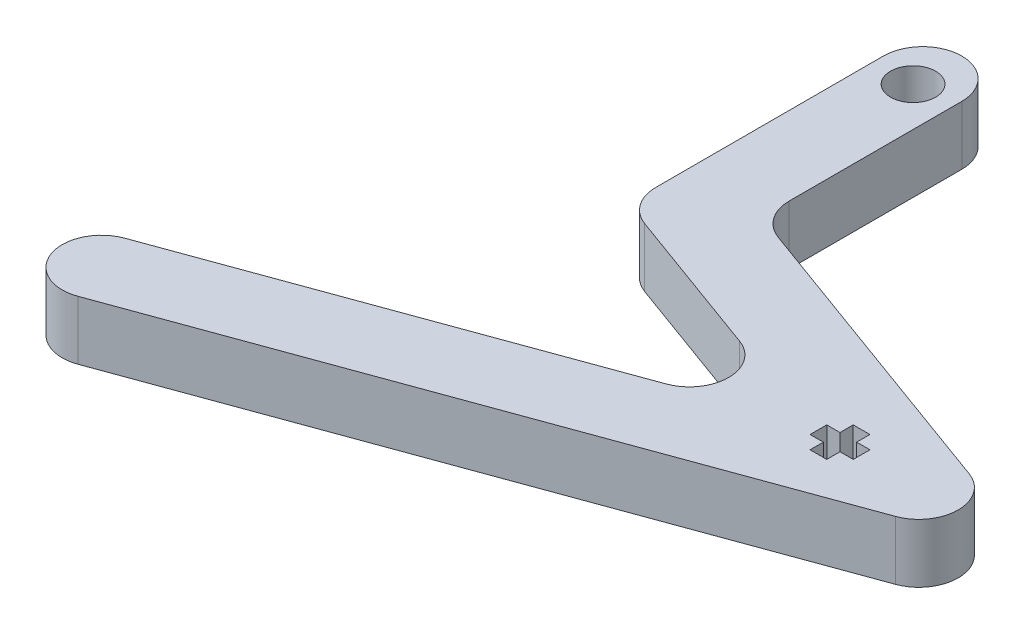
SolidWorks part; units mm, degrees
ref_plane "Front Plane" through (0, 0, 0) normal (0, 0, 1) x (1, 0, 0)
ref_plane "Top Plane" through (0, 0, 0) normal (0, 1, 0) x (1, 0, 0)
ref_plane "Right Plane" through (0, 0, 0) normal (1, 0, 0) x (0, 0, -1)
sketch "Sketch1" plane through (0, 0, 0) normal (0, 1, 0) x (1, 0, 0)
  line L16 (-80.6848, 38.8147) -> (-80.6848, 8.8147)
  line L19 (-72.6848, 14.4164) -> (-72.6848, 38.8147)
  line L22 (-72.6848, 14.4164) -> (-29.1036, -1.4459)
  line L26 (-80.6848, 8.8147) -> (-52.494, -1.4459)
  line L27 (-52.494, -1.4459) -> (-107.0151, -21.29)
  line L28 (-107.0151, -21.29) -> (-104.279, -28.8075)
  line L29 (-104.279, -28.8075) -> (-29.1036, -1.4459)
  line L30 (-80.6848, 38.8147) -> (-72.6848, 38.8147)
  line L43 (-51.0109, -0.6289) -> (-51.0109, -2.3289)
  line L44 (-51.0109, -2.3289) -> (-49.6609, -2.3289)
  line L45 (-49.6609, -2.3289) -> (-49.6609, -3.6789)
  line L46 (-49.6609, -3.6789) -> (-47.9609, -3.6789)
  line L47 (-47.9609, -3.6789) -> (-47.9609, -2.3289)
  line L48 (-47.9609, -2.3289) -> (-46.6109, -2.3289)
  line L49 (-46.6109, -2.3289) -> (-46.6109, -0.6289)
  line L50 (-46.6109, -0.6289) -> (-47.9609, -0.6289)
  line L51 (-47.9609, -0.6289) -> (-47.9609, 0.7211)
  line L52 (-47.9609, 0.7211) -> (-49.6609, 0.7211)
  line L53 (-49.6609, 0.7211) -> (-49.6609, -0.6289)
  line L54 (-49.6609, -0.6289) -> (-51.0109, -0.6289)
  circle A46 centre (-76.6848, 33.8437) radius 2.3
  circle A47 centre (-48.8109, -1.4789) radius 2.3585 construction
  point P44 (-76.6848, 38.8147)
  dimension "D2" = 1.7
  dimension "D3" = 8
  dimension "D1" = 1.35
  dimension "D8" = 4.6
  dimension "D4" = 110
  dimension "D5" = 40
  dimension "D6" = 8
  dimension "D7" = 8
  dimension "D10" = 30
  dimension "D11" = 80
  dimension "D12" = 30
extrude "Boss-Extrude1" add sketch "Sketch1" along normal blind 6
fillet "Fillet1" radius 4 8 edges at (-72.6848, 3, -14.4164) (-80.6848, 3, -8.8147) (-104.279, 3, 28.8075) (-107.0151, 3, 21.29) (-52.494, 3, 1.4459) (-29.1036, 3, 1.4459) (-72.6848, 3, -38.8147) (-80.6848, 3, -38.8147)
